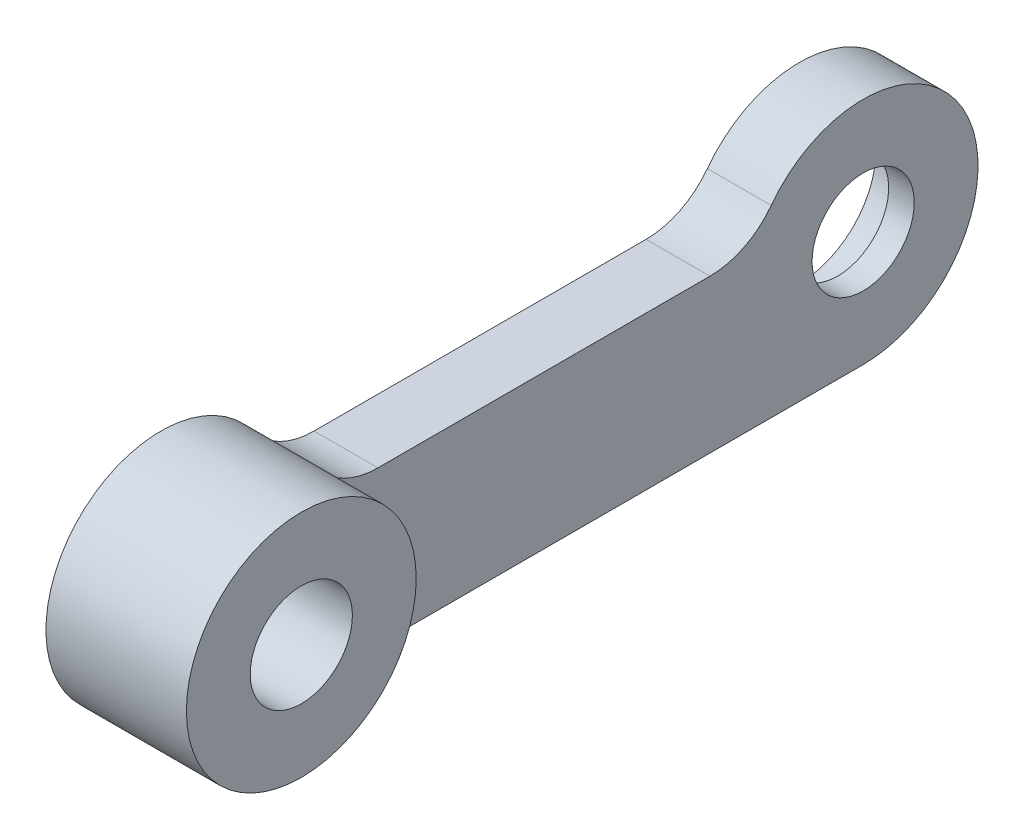
SolidWorks part; units mm, degrees
ref_plane "前视基准面" through (0, 0, 0) normal (0, 0, 1) x (1, 0, 0)
ref_plane "上视基准面" through (0, 0, 0) normal (0, 1, 0) x (1, 0, 0)
ref_plane "右视基准面" through (0, 0, 0) normal (1, 0, 0) x (0, 0, -1)
other "Configuration Table"
sketch "草图1" plane through (0, 0, 0) normal (1, 0, 0) x (0, 0, -1)
  line L1 (0, 0) -> (25, 0)
  line L2 (0, 0) -> (0, -6)
  line L3 (0, -6) -> (25, -6)
  line L4 (25, 0) -> (25, -6)
  circle A0 centre (0, -1.5) radius 4.5
  circle A1 centre (25, -1.5) radius 4.5
  circle A2 centre (0, -1.5) radius 2
  circle A3 centre (25, -1.5) radius 2
  dimension "D1" = 9
  dimension "D2" = 9
  dimension "D4" = 4
  dimension "D3" = 6
  dimension "D5" = 25
extrude "凸台-拉伸1" add sketch "草图1" along normal blind 2.5 contours A0 | L1 L4 L3 L2 | A1
extrude "凸台-拉伸3" add sketch "草图1<5>" along normal blind 3 from surface contours A0 starting at face at (2.5, -0.951, -12.5)
sketch "草图1<5>" plane through (0, 0, 0) normal (1, 0, 0) x (0, 0, -1) same geometry as "草图1"
extrude "切除-拉伸2" cut sketch "草图1<4>" along normal through all both and the other way through all contours L2 A2 | L2 A2 | L4 A3 L1 | L1 A3 L4 region at (0, -1.3854, 0.7577) region at (0, -1.6324, -0.8755) region at (0, -1.3854, -25.7577) region at (0, -1.6324, -24.1245)
sketch "草图1<4>" plane through (0, 0, 0) normal (1, 0, 0) x (0, 0, -1) same geometry as "草图1"
fillet "圆角1" radius 3 2 edges at (1.25, 0, -20.7574) (1.25, 0, -4.2426)
sketch "草图2" plane through (0, 0, 0) normal (-1, 0, 0) x (0, 0, 1)
  circle A0 centre (-25, -1.5) radius 3
  circle A1 centre (0, -1.5) radius 3
  dimension "D1" = 6
extrude "切除-拉伸3" cut sketch "草图2" against normal blind 1.5
